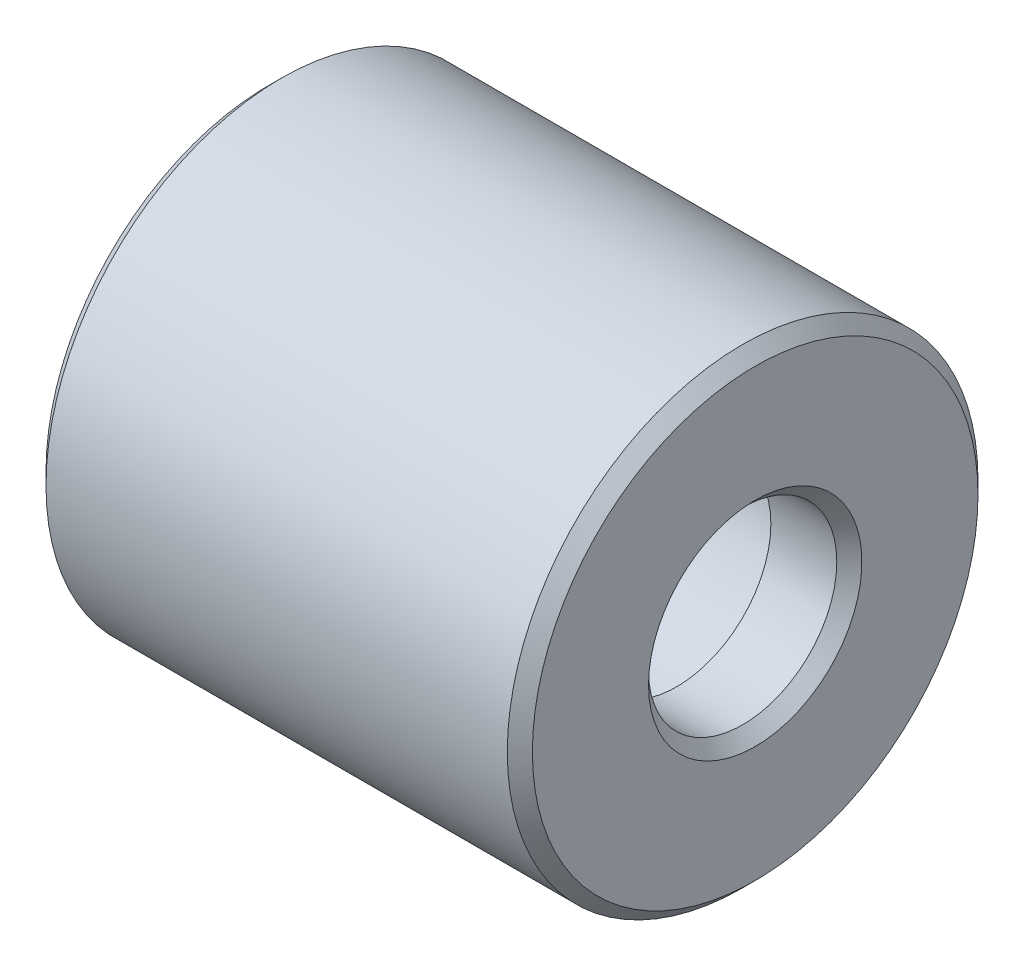
SolidWorks part; units mm, degrees
material "6061-T6 (SS)"
ref_plane "Front Plane" through (0, 0, 0) normal (0, 0, 1) x (1, 0, 0)
ref_plane "Top Plane" through (0, 0, 0) normal (0, 1, 0) x (1, 0, 0)
ref_plane "Right Plane" through (0, 0, 0) normal (1, 0, 0) x (0, 0, -1)
sketch "Sketch1" plane through (0, 0, 0) normal (0, 0, 1) x (1, 0, 0)
  line L0 (0, 5.5562) -> (0, 0) construction
  line L1 (0, 5.5562) -> (16.51, 5.5562)
  line L2 (16.51, 5.5562) -> (16.51, 3.81)
  line L3 (16.51, 3.81) -> (19.685, 3.81)
  line L4 (19.685, 3.81) -> (19.685, 9.525)
  line L5 (19.685, 9.525) -> (0, 9.525)
  line L6 (0, 9.525) -> (0, 5.5562)
  line L7 (0, 0) -> (44.5396, 0) construction
  point P3 (10.8556, 1.7397)
  dimension "D1" = 11.1125
  dimension "D2" = 19.05
  dimension "D3" = 3.175
  dimension "D4" = 7.62
  dimension "D5" = 16.51
revolve "Revolve1" add sketch "Sketch1" angle 360 about L7
chamfer "Chamfer1" distance 0.508 angle 45 4 edges at (19.685, 0, 3.81) (0, 0, 5.5562) (19.685, 0, 9.525) (0, 0, 9.525)
equation "\"D1@Sketch1\"=7in/16"
equation "\"D4@Sketch1\"=0.25in+0.05in"
